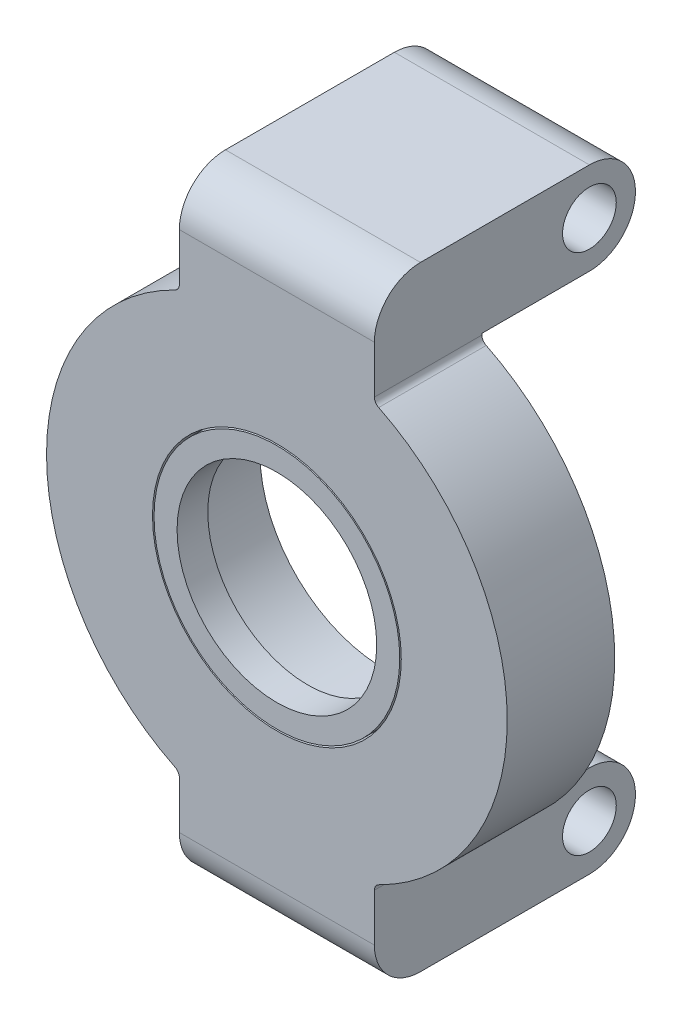
SolidWorks part; units mm, degrees
ref_plane "Alzado" through (0, 0, 0) normal (0, 0, 1) x (1, 0, 0)
ref_plane "Planta" through (0, 0, 0) normal (0, 1, 0) x (1, 0, 0)
ref_plane "Vista lateral" through (0, 0, 0) normal (1, 0, 0) x (0, 0, -1)
sketch "Croquis1" plane through (0, 0, 0) normal (0, 0, 1) x (1, 0, 0)
  line L18 (-6.35, -20) -> (6.35, -20)
  line L19 (-6.35, -20) -> (-6.35, -13.5896)
  line L20 (-6.35, 20) -> (6.35, 20)
  line L21 (6.35, -20) -> (6.35, -13.5896)
  line L22 (-6.35, -20) -> (6.35, 20) construction
  line L23 (-6.35, 20) -> (6.35, -20) construction
  line L24 (-6.35, 13.5896) -> (-6.35, 20)
  line L25 (6.35, 13.5896) -> (6.35, 20)
  circle A2 centre (0, 0) radius 8.1
  arc A8 (-6.35, 13.5896) -> (-6.35, -13.5896) centre (0, 0) ccw
  arc A9 (6.35, -13.5896) -> (6.35, 13.5896) centre (0, 0) ccw
  dimension "D1" = 16.2
  dimension "D2" = 12.7
  dimension "D3" = 40
  dimension "D4" = 30
extrude "Saliente-Extruir4" add sketch "Croquis1" along normal blind 7
sketch "Croquis5" plane through (0, 0, 0) normal (0, 0, -1) x (-1, 0, 0)
  line L0 (0, 0) -> (-0.2462, 20) construction
  line L33 (6.35, 20) -> (6.35, 13.5896) construction
  line L38 (-6.35, 20) -> (6.35, 20)
  line L39 (-6.35, 20) -> (-6.35, 14)
  line L40 (6.5, 0) -> (-5.7688, 0) construction
  line L53 (-6.35, 14) -> (6.35, 14)
  line L54 (6.35, 20) -> (6.35, 14)
  line L55 (6.35, -13.5896) -> (6.35, -20) construction
  line L56 (-6.35, -20) -> (6.35, -20)
  line L57 (-6.35, -20) -> (-6.35, -14)
  line L58 (-6.35, -14) -> (6.35, -14)
  line L59 (6.35, -20) -> (6.35, -14)
  dimension "D1" = 14
  dimension "D2" = 14
extrude "Saliente-Extruir5" add sketch "Croquis5" along normal blind 10
fillet "Redondeo1" radius 3 4 edges at (0, 14, -10) (0, 20, -10) (0, -14, -10) (0, -20, -10)
sketch "Croquis7" plane through (6.35, 0, 0) normal (1, 0, 0) x (0, 0, -1)
  circle A0 centre (7, 17) radius 1.75
  circle A1 centre (7, -17) radius 1.75
  dimension "D1" = 3.5
  dimension "D2" = 3.5
extrude "Cortar-Extruir1" cut sketch "Croquis7" against normal through all
sketch "Croquis8" plane through (0, 0, 7) normal (0, 0, 1) x (1, 0, 0)
  line L0 (-6.35, 20) -> (6.35, -20) construction
  circle A0 centre (0, 0) radius 8
  circle A1 centre (0, 0) radius 6.5
  dimension "D1" = 13
extrude "Saliente-Extruir6" add sketch "Croquis8" against normal blind 2
fillet "Redondeo3" radius 3 2 edges at (0, -20, 7) (0, 20, 7)
fillet "Redondeo4" radius 0.5 4 edges at (-6.35, 13.5896, 3.5) (-6.35, -13.5896, 3.5) (6.35, -13.5896, 3.5) (6.35, 13.5896, 3.5)
